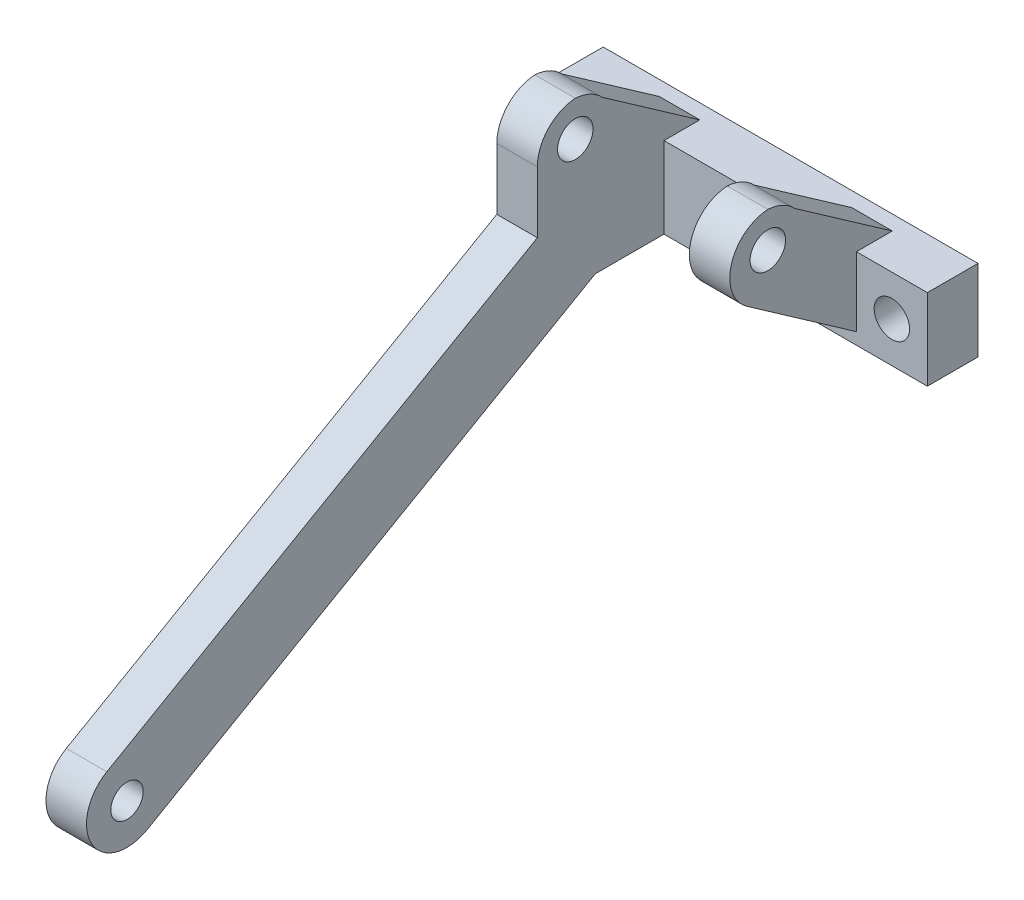
SolidWorks part; units mm, degrees
ref_plane "Front Plane" through (0, 0, 0) normal (0, 0, 1) x (1, 0, 0)
ref_plane "Top Plane" through (0, 0, 0) normal (0, 1, 0) x (1, 0, 0)
ref_plane "Right Plane" through (0, 0, 0) normal (1, 0, 0) x (0, 0, -1)
sketch "Sketch1" plane through (0, 0, 0) normal (0, 0, 1) x (1, 0, 0)
  line L0 (15, 0) -> (-15, 0) construction
  line L1 (-18.5, 4) -> (18.5, 4)
  line L2 (-18.5, 4) -> (-18.5, -4)
  line L3 (-18.5, -4) -> (18.5, -4)
  line L4 (18.5, 4) -> (18.5, -4)
  line L5 (-18.5, 4) -> (18.5, -4) construction
  line L6 (-18.5, -4) -> (18.5, 4) construction
  line L7 (0, -4) -> (0, 4) construction
  circle A0 centre (-15, 0) radius 1.75
  circle A1 centre (15, 0) radius 1.75
  point P0 (0, 0)
  point P12 (0, 0)
  dimension "D3" = 3.5
  dimension "D1" = 37
  dimension "D2" = 8
  dimension "D4" = 15
extrude "Boss-Extrude1" add sketch "Sketch1" along normal blind 5
sketch "Sketch2" plane through (0, 0, 5) normal (0, 0, 1) x (1, 0, 0)
  line L0 (0, 4) -> (0, -4) construction
  line L1 (18.5, 4) -> (-18.5, 4) construction
  line L2 (-18.5, -4) -> (18.5, -4) construction
  line L3 (11.5, -4) -> (7.5, 4) construction
  line L4 (-11.5, 4) -> (-7.5, 4)
  line L5 (-11.5, 4) -> (-11.5, -4)
  line L6 (-11.5, -4) -> (-7.5, -4)
  line L7 (-7.5, 4) -> (-7.5, -4)
  line L8 (-11.5, 4) -> (-7.5, -4) construction
  line L9 (-11.5, -4) -> (-7.5, 4) construction
  line L10 (11.5, 4) -> (7.5, -4) construction
  line L11 (7.5, 4) -> (7.5, -4)
  line L12 (11.5, -4) -> (7.5, -4)
  line L13 (11.5, 4) -> (11.5, -4)
  line L14 (11.5, 4) -> (7.5, 4)
  point P6 (-9.5, 0)
  point P15 (9.5, 0)
  dimension "D1" = 7.5
  dimension "D2" = 4
extrude "Boss-Extrude2" add sketch "Sketch2" along normal blind 12.5
sketch "Sketch4" plane through (0, 4, 0) normal (0, 1, 0) x (1, 0, 0)
  line L0 (-7.5, -17.5) -> (-7.5, -5) construction
  line L1 (-11.5, -17.5) -> (-7.5, -17.5)
  line L2 (-11.5, -17.5) -> (-11.5, -10)
  line L3 (-11.5, -10) -> (-7.5, -10)
  line L4 (-7.5, -17.5) -> (-7.5, -10)
  line L5 (0, 0) -> (0, -5) construction
  line L6 (7.5, -5) -> (-7.5, -5) construction
  line L7 (7.5, -17.5) -> (7.5, -10)
  line L8 (11.5, -10) -> (7.5, -10)
  line L9 (11.5, -17.5) -> (11.5, -10)
  line L10 (11.5, -17.5) -> (7.5, -17.5)
  dimension "D1" = 7.5
extrude "Boss-Extrude3" add sketch "Sketch4" along normal blind 8
sketch "Sketch3" plane through (-11.5, 0, 0) normal (-1, 0, 0) x (0, 0, 1)
  line L0 (10, 8.5) -> (17.5, 8.5) construction
  line L4 (10, 12) -> (10, 4) construction
  line L5 (17.5, 12) -> (17.5, -4) construction
  line L6 (13.75, 8.5) -> (13.75, 12) construction
  line L7 (10, 12) -> (17.5, 12) construction
  circle A0 centre (13.75, 8.5) radius 1.75
  dimension "D1" = 3.5
  dimension "D2" = 8.5
extrude "Cut-Extrude1" cut sketch "Sketch3" against normal through all
fillet "Fillet1" radius 4 4 edges at (-9.5, 12, 10) (9.5, 12, 10) (9.5, 12, 17.5) (-9.5, 12, 17.5)
sketch "Sketch5" plane through (-7.5, 0, 0) normal (1, 0, 0) x (0, 0, -1)
  line L0 (-10, 8) -> (-10, 4) construction
  line L1 (-10, 6.5) -> (-13, 6.5)
  line L2 (-10, 6.5) -> (-10, 1.5)
  line L3 (-10, 1.5) -> (-13, 1.5)
  line L4 (-13, 6.5) -> (-13, 1.5)
  line L5 (-10, 4) -> (-5, 4) construction
  dimension "D1" = 3
  dimension "D2" = 5
  dimension "D3" = 2.5
extrude "Boss-Extrude4" [suppressed] add sketch "Sketch5" along normal up to next
sketch "Sketch6" plane through (-11.5, 0, 0) normal (-1, 0, 0) x (0, 0, 1)
  line L0 (56.0113, -29.4012) -> (11.7824, -4)
  line L1 (17.5, -4) -> (5, -4) construction
  line L2 (11.7824, -4) -> (17.5, 1.9418)
  line L3 (13.75, 8.5) -> (58.0033, -25.9326) construction
  line L4 (17.5, 1.9418) -> (59.9954, -22.4639)
  line L5 (59.9954, -22.4639) -> (56.0113, -29.4012) construction
  line L6 (13.75, 8.5) -> (13.75, -4) construction
  line L7 (17.5, 8) -> (17.5, -4) construction
  circle A0 centre (58.0033, -25.9326) radius 1.6
  arc A1 (56.0113, -29.4012) -> (59.9954, -22.4639) centre (58.0033, -25.9326) ccw
  dimension "D1" = 3.2
  dimension "D2" = 8
  dimension "D3" = 52.114
  dimension "D4" = 56.071
  dimension "D5" = 1.9676
extrude "Boss-Extrude5" add sketch "Sketch6" against normal up to surface (4 mm away) up to face at (-7.5, 6.75, 13.75)
sketch "Sketch7" plane through (-11.5, 0, 0) normal (-1, 0, 0) x (0, 0, 1)
  line L0 (1.4608, 4) -> (11.0845, 10.7386)
  line L1 (5, 4) -> (0, 4) construction
  line L2 (11.0845, 10.7386) -> (10, 4)
  line L3 (10, 8) -> (10, 4) construction
  line L4 (10, 4) -> (1.4608, 4)
  arc A0 (13.75, 11.9922) -> (10, 8) centre (14, 8) ccw construction
  dimension "D1" = 35
extrude "Boss-Extrude6" add sketch "Sketch7" against normal up to surface (4 mm away) up to face at (-7.5, -2.4438, 21.5899)
sketch "Sketch8" plane through (11.5, 0, 0) normal (1, 0, 0) x (0, 0, -1)
  line L0 (-1.4608, 4) -> (-11.0845, 10.7386)
  line L1 (-11.0845, 10.7386) -> (-10, 4)
  line L2 (-10, 4) -> (-1.4608, 4)
  arc A0 (-10, 8) -> (-13.75, 11.9922) centre (-14, 8) ccw construction
extrude "Boss-Extrude7" add sketch "Sketch8" against normal up to surface (4 mm away) up to face at (7.5, 10.25, 13.75)
sketch "Sketch9" plane through (11.5, 0, 0) normal (1, 0, 0) x (0, 0, -1)
  line L0 (-15.7943, 4.7234) -> (-5, -2.8349)
  line L1 (-5, -4) -> (-5, 4) construction
  line L2 (-5, -2.8349) -> (-5, -4)
  line L3 (-5, -4) -> (-17.5, -4)
  line L4 (-17.5, -4) -> (-17.5, 8) construction
  line L5 (-17.5, -4) -> (-5, -4) construction
  line L6 (-17.5, -4) -> (-17.5, 8)
  line L7 (-1.4608, 4) -> (-11.0845, 10.7386) construction
  arc A0 (-17.5, 8) -> (-15.7943, 4.7234) centre (-13.5, 8) ccw
  arc A1 (-13.75, 11.9922) -> (-17.5, 8) centre (-13.5, 8) ccw construction
  point P2 (-15.4819, 5.7065)
  point P5 (-15.3495, 5.4084)
  point P19 (-15.4925, 5.4867)
  point P22 (-14.363, 4.6799)
  point P23 (-15.7631, 5.6603)
  point P24 (-15.7465, 5.6487)
  point P25 (-13.75, 8.5)
  point P26 (0, 0)
extrude "Cut-Extrude2" cut sketch "Sketch9" against normal up to next
equation "\"X-ROD-SPACING\"=45"
equation "\"Y-ROD-SPACING\"=75"
equation "\"Z-ROD-SPACING\"=17.5"
equation "\"Y-BED-OFFSET\"=2"
equation "\"Y-BED-ROD-INSET\"=3.5"
equation "\"Y-BED-SCREW-SPACING\"=209"
equation "\"Y-BED-SCREW-CUTOUT-SLOT-HEIGHT\"=2.5"
equation "\"T-SLOT-NUT-FILLET-RADIUS\"=0.5"
equation "\"T-SLOT-SCREW-SHAFT-RADIUS\"=1.55"
equation "\"T-SLOT-SCREW-SHAFT-CUTOUT-LENGTH\"=11"
equation "\"T-SLOT-NUT-DEPTH\"=3.5"
equation "\"T-SLOT-NUT-WIDTH\"=2.85"
equation "\"T-SLOT-NUT-END-DISTANCE\"=8"
equation "\"ACRYLIC-THICKNESS\"=10"
equation "\"ACRYLIC-THICKNESS2\"=4.5"
equation "\"ACRYLIC-TAB-CUTOUT-SIZE\"=\"ACRYLIC-THICKNESS\"+\"ACRYLIC-TAB-TOLERANCE\"*2"
equation "\"ACRYLIC-TAB-TOLERANCE\"=-.05"
equation "\"ACRYLIC-TAB-WIDTH\"=\"ACRYLIC-THICKNESS\""
equation "\"ACRYLIC-M3-HOLE\"=2.9"
equation "\"SMOOTHROD-CAP-SCREW-DISTANCE\"=20"
equation "\"FRAME-WIDTH-INNER\"=370"
equation "\"NEMA17-HOLE-SPACING\"=31"
equation "\"NEMA17-CENTRAL-CUTOUT\"=22.5"
equation "\"Z-BRACKET-REACH\"=57"
equation "\"Z-ROD-INSET\"=13.5"
equation "\"TOP-BRACKET-SPACING\"=40"
equation "\"SMOOTHROD-X-LENGTH\"=350"
equation "\"SMOOTHROD-Y-LENGTH\"=350"
equation "\"SMOOTHROD-Z-LENGTH\"=350"
equation "\"SMOOTHROD-TIGHTENING-HEADROOM\"=.25"
equation "\"LEADSCREW-Z-LENGTH\"=300"
equation "\"SCREW-LENGTH-FRAME\"=\"ACRYLIC-THICKNESS\" + 10"
equation "\"SCREW-LENGTH-MOTOR\"=\"ACRYLIC-THICKNESS\" + 5"
equation "\"SCREW-LENGTH-EXTRUDER\"=28"
equation "\"SCREW-HEAD-RADIUS\"=6"
equation "\"PRINTED-X-SMOOTHROD-DIAMETER\"=8.8"
equation "\"PRINTED-X-SMOOTHROD-CUTOUT\"=10"
equation "\"PRINTED-X-BASE-HEIGHT\"=10"
equation "\"PRINTED-LM8UU-CUTOUT-SIZE\"=15.5"
equation "\"PRINTED-LM8UU-CUTOUT-LENGTH\"=24.5"
equation "\"PRINTED-X-IDLER-HEIGHT\"=16"
equation "\"PSU-MOUNTING-WIDTH\"=95"
equation "\"PSU-MOUNTING-HEIGHT\"=177"
equation "\"Y-BELT-TO-ROD-DISTANCE\"=20"
equation "\"SPOOL-HOLDER-ROD-SPACING\"=150"
equation "\"ACRYLIC-X-CARRIAGE-WIDTH\"=55"
equation "\"ACRYLIC-X-CARRIAGE-HEIGHT\"=75"
equation "\"ACRYLIC-X-CARRIAGE-LM8UU-CUTOUT-WIDTH\"=24.25"
equation "\"ACRYLIC-X-CARRIAGE-LM8UU-CUTOUT-HEIGHT\"=11.0"
equation "\"ACRYLIC-X-CARRIAGE-SCREW-SPACING-X\"=15"
equation "\"ACRYLIC-X-CARRIAGE-SCREW-SPACING-Y\"=33"
equation "\"ACRYLIC-X-CARRIAGE-CENTER-TAB-SPACING\"=14"
equation "\"ACRYLIC-X-CARRIAGE-EXTRUDER-OFFSET\"=26"
equation "\"ACRYLIC-X-CARRIAGE-EXTRUDER-ANGLE\"=90"
equation "\"ACRYLIC-X-CARRIAGE-EXTRUDER-SHELF-DEPTH\"=\"ACRYLIC-X-CARRIAGE-EXTRUDER-OFFSET\" + 28"
equation "\"ACRYLIC-X-CARRIAGE-EXTRUDER-BRACE-SPACING\"=23"
equation "\"ACRYLIC-X-CARRIAGE-EXTRUDER-BRACE-TAB-OFFSET\"=20"
equation "\"ACRYLIC-X-CARRIAGE-EXTRUDER-BRACE-HEIGHT\"=35"
equation "\"ACRYLIC-X-CARRIAGE-EXTRUDER-BRACE-SCREW-SPACING\"=22"
equation "\"ACRYLIC-X-CARRIAGE-DUAL-WIDTH-MULTIPLIER\"=1.65"
equation "\"ACRYLIC-X-CARRIAGE-DUAL-HOTEND-SPACING\"=42"
equation "\"ACRYLIC-X-CARRIAGE-DUAL-WIDTH\"=75"
equation "\"ACRYLIC-X-CARRIAGE-DUAL-HOTEND-SEPARATION\"=36"
equation "\"ACRYLIC-X-CARRIAGE-DUAL-MOUNT-PLATE-DEPTH\"=75"
equation "\"ACRYLIC-X-CARRIAGE-DUAL-MOUNT-BRACE-WIDTH\"=33"
equation "\"ACRYLIC-X-CARRIAGE-DUAL-MOUNT-SCREW-WIDTH\"=40"
equation "\"D3@Sketch1\"=3.5"
equation "\"PRINTED-M3-HOLE\"=3.5"
equation "\"BLOWER-FAN-WIDTH\"=15"
equation "\"D1@Sketch2\"=\"BLOWER-FAN-WIDTH\"/2"
